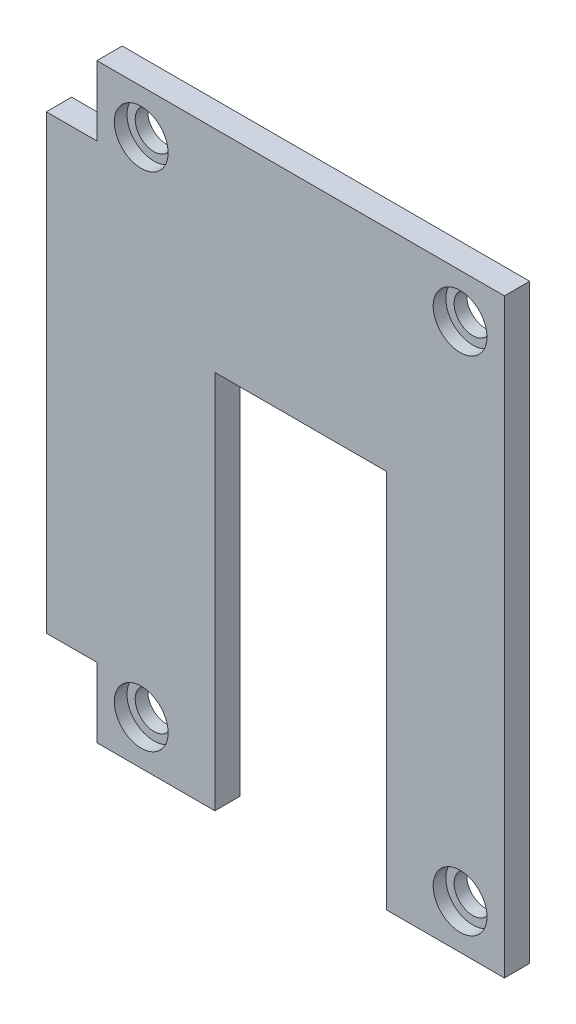
SolidWorks part; units mm, degrees
ref_plane "Alzado" through (0, 0, 0) normal (0, 0, 1) x (1, 0, 0)
ref_plane "Planta" through (0, 0, 0) normal (0, 1, 0) x (1, 0, 0)
ref_plane "Vista lateral" through (0, 0, 0) normal (1, 0, 0) x (0, 0, -1)
sketch "Croquis1" plane through (0, 0, 0) normal (0, 0, 1) x (1, 0, 0)
  line L0 (0, 93.345) -> (64.3868, 93.345)
  line L1 (0, 93.345) -> (0, 0)
  line L2 (0, 0) -> (64.3868, 0)
  line L3 (64.3868, 93.345) -> (64.3868, 0)
  dimension "D1" = 64.3868
  dimension "D2" = 93.345
extrude "Saliente-Extruir1" add sketch "Croquis1" along normal blind 4
sketch "Croquis2" plane through (0, 0, 4) normal (0, 0, 1) x (1, 0, 0)
  line L5 (0, 0) -> (64.3868, 0) construction
  line L6 (18.63, 0) -> (45.7568, 0)
  line L7 (18.63, 0) -> (18.63, 60)
  line L8 (18.63, 60) -> (45.7568, 60)
  line L9 (45.7568, 0) -> (45.7568, 60)
  line L10 (64.3868, 0) -> (64.3868, 93.345) construction
  line L11 (0, 93.345) -> (0, 0) construction
  dimension "D1" = 18.63
  dimension "D2" = 18.63
  dimension "D3" = 60
extrude "Cortar-Extruir1" cut sketch "Croquis2" against normal through all
sketch "Croquis5" plane through (0, 0, 4) normal (0, 0, 1) x (1, 0, 0)
  line L0 (64.3868, 0) -> (64.3868, 93.345) construction
  line L1 (64.3868, 93.345) -> (0, 93.345) construction
  line L2 (0, 93.345) -> (0, 0) construction
  line L3 (45.7568, 0) -> (64.3868, 0) construction
  circle A0 centre (57.3868, 86.345) radius 4.25
  circle A1 centre (7, 86.345) radius 4.25
  circle A2 centre (57.3868, 7) radius 4.25
  circle A3 centre (7, 7) radius 4.25
  point P14 (0, 0)
  point P15 (0, 0)
  point P18 (0, 0)
  dimension "D5" = 8.5
  dimension "D1" = 7
  dimension "D2" = 7
  dimension "D3" = 7
  dimension "D4" = 7
  dimension "D6" = 7
extrude "Cortar-Extruir3" cut sketch "Croquis5" against normal blind 2
sketch "Croquis6" plane through (0, 0, 2) normal (0, 0, 1) x (1, 0, 0)
  circle A0 centre (7, 86.345) radius 2.95
  circle A1 centre (57.3868, 86.345) radius 2.95
  circle A2 centre (57.3868, 7) radius 2.95
  circle A3 centre (7, 7) radius 2.95
  dimension "D1" = 5.9
extrude "Cortar-Extruir4" cut sketch "Croquis6" against normal through all
sketch "Croquis7" plane through (0, 0, 0) normal (0, 0, -1) x (-1, 0, 0)
  line L0 (0, 11) -> (0, 82.345)
  line L3 (0, 11) -> (8, 11)
  line L4 (8, 82.345) -> (8, 11)
  line L5 (0, 93.345) -> (0, 0) construction
  line L6 (0, 82.345) -> (8, 82.345)
  line L7 (-64.3868, 93.345) -> (0, 93.345) construction
  dimension "D1" = 8
  dimension "D2" = 11
  dimension "D3" = 11
extrude "Saliente-Extruir4" add sketch "Croquis7" against normal through all
